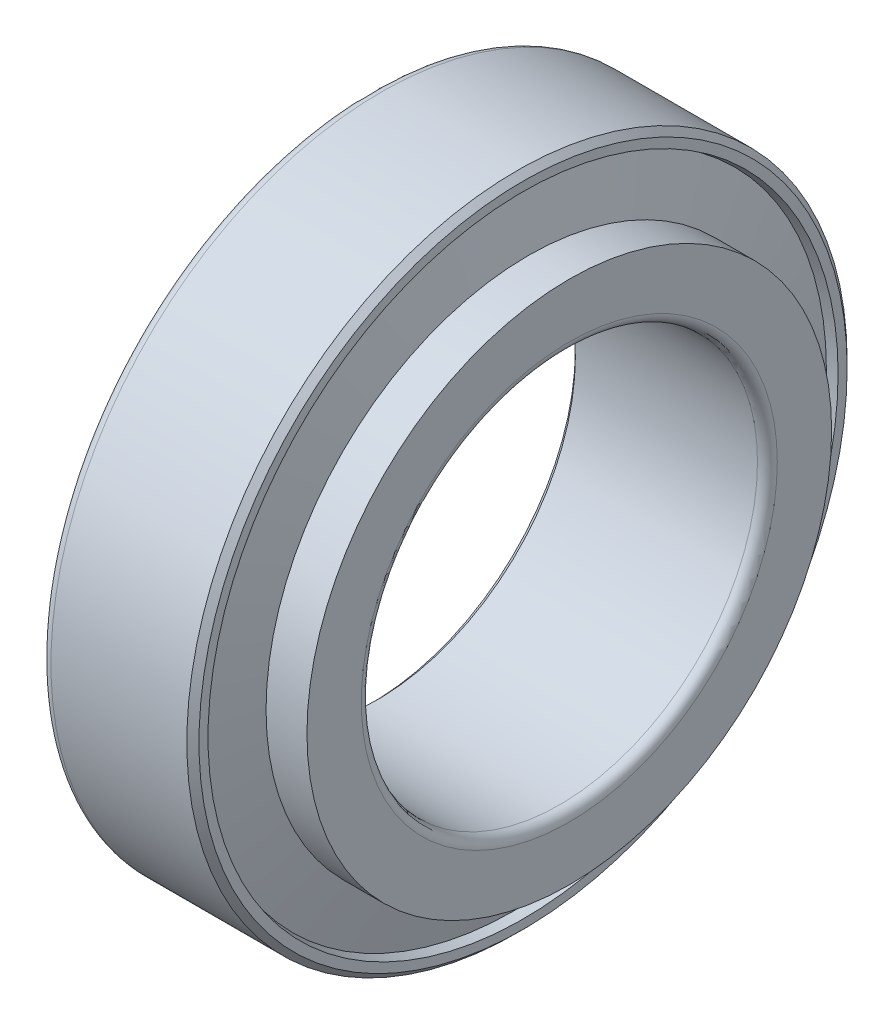
SolidWorks part; units mm, degrees
revolve "OuterRace" add sketch "OutRacSke" angle 360 about L5 other way angle 28.04 reverse direction yes
sketch "OutRacSke" plane through (0, 0, 0) normal (0, 0, 1) x (1, 0, 0)
  line L0 (-7, 47.7097) -> (-30, 41.7615)
  line L1 (-30, 41.7615) -> (-30, 48.5)
  line L2 (-28.5, 50) -> (-7.92, 50)
  line L3 (-7.92, 50) -> (-7, 49.08)
  line L4 (-7, 49.08) -> (-7, 47.7097)
  line L5 (-42.5, 0) -> (42.5, 0) construction
  arc A0 (-30, 48.5) -> (-28.5, 50) centre (-28.5, 48.5) cw
  dimension "D8" = 45
  dimension "Tangle" = 14.5
ref_plane "Plane1" through (0, 0, 0) normal (0, 0, 1) x (1, 0, 0)
ref_plane "Plane2" through (0, 0, 0) normal (0, 1, 0) x (1, 0, 0)
ref_plane "Plane3" through (0, 0, 0) normal (1, 0, 0) x (0, 0, -1)
sketch "Clipboard" plane through (0, 0, 0) normal (0, 0, 1) x (1, 0, 0)
  line L0 (0, 0) -> (10, 0) construction
  line L1 (0, 0) -> (83.4721, -2.9149)
  line L2 (0, 0) -> (59.9634, 2.094)
  line L3 (0, 0) -> (99.9391, -3.4899)
  line L4 (0, 0) -> (-20.6968, -0.3613)
  line L5 (0, 0) -> (-9, 30)
  dimension "Roller_diameter" = 9
  dimension "cyl_len" = 20.7
sketch "RolDetSke" plane through (0, 0, 0) normal (0, 0, 1) x (1, 0, 0)
  line L0 (-27.3733, 38.0035) -> (-28.5, 42.3602)
  line L1 (-27.3733, 38.0035) -> (-7.3326, 43.1864)
  line L2 (-8.4593, 47.543) -> (-7.3326, 43.1864)
  line L4 (-44.5664, 33.5571) -> (5.2024, 46.4281) construction
  line L5 (-8.4593, 47.543) -> (-28.5, 42.3602)
  line L9 (-7, 47.7097) -> (-30, 41.7615) construction
  dimension "Roller_diameter" = 9
  dimension "dy" = 42.3602
  dimension "D2" = 28.5
  dimension "cyl_len" = 20.7
revolve "RollerDetailed" [suppressed] add sketch "RolDetSke" angle 360 about L4 reverse direction yes
sketch "RolSimSke" plane through (0, 0, 0) normal (0, 0, 1) x (1, 0, 0)
  line L0 (0, 0) -> (-32, 0) construction
  line L1 (-28.5, 42.3602) -> (-8.4593, 47.543)
  line L2 (-28.5, 42.3602) -> (-26.2466, 33.6468)
  line L3 (-26.2466, 33.6468) -> (-6.2059, 38.8297)
  line L4 (-8.4593, 47.543) -> (-6.2059, 38.8297)
  dimension "Roller_diameter" = 9
  dimension "dy" = 42.3602
  dimension "dx" = 28.5
  dimension "Tangle" = 14.5
revolve "RollersSimplified" add sketch "RolSimSke" angle 360 about L0
ref_axis "Axis1" through (-50, 0, 0) along (1, 0, 0)
pattern_circular "RollersDetailed" [suppressed] count 2 every 180 about axis through (-50, 0, 0) along (1, 0, 0)
sketch "InsRacSke" plane through (0, 0, 0) normal (0, 0, 1) x (1, 0, 0)
  line L0 (-26.3517, 34.0968) -> (-30, 34.0968)
  line L1 (-30, 48.5) -> (-30, -48.5) construction
  line L2 (-30, 34.0968) -> (-30, 30.92)
  line L3 (-30, 30.92) -> (-29.08, 30)
  line L4 (-29.08, 30) -> (-1.5, 30)
  line L5 (0, 31.5) -> (0, 39.7297)
  line L6 (0, 39.7297) -> (-6.1947, 39.7297)
  line L7 (-6.1947, 39.7297) -> (-6.1947, 38.8297)
  line L8 (-6.1947, 38.8297) -> (-26.2353, 33.6468)
  line L9 (-26.2353, 33.6468) -> (-26.3517, 34.0968)
  line L10 (-42.5, 0) -> (42.5, 0) construction
  arc A0 (-1.5, 30) -> (0, 31.5) centre (-1.5, 31.5) ccw
  dimension "Tangle" = 14.5
  dimension "cyl_len" = 20.7
  dimension "dy" = 33.6468
  dimension "dx" = 26.2353
  dimension "D11" = 45
  dimension "D2" = 30
revolve "InnerRace" add sketch "InsRacSke" angle 360 about L10 reverse direction yes
sketch "CagSpiSke" plane through (0, 0, 0) normal (0, 0, 1) x (1, 0, 0)
  line L3 (-6.3306, 43.2348) -> (-27.3733, 37.7928)
  line L4 (-27.804, 37.0616) -> (-27.5035, 35.8999)
  line L6 (-42.5, 0) -> (42.5, 0) construction
  arc A1 (-27.3733, 37.7928) -> (-27.804, 37.0616) centre (-27.2231, 37.2119) ccw
  dimension "Tangle" = 14.5
  dimension "radius" = 0.6
  dimension "dx" = 27.3733
  dimension "dy" = 37.7928
  dimension "offset" = 1.8
revolve "CageSpine" [suppressed] add sketch "CagSpiSke" angle 0.001 about L6 wall 1.5
equation "\"OD@OutRacSke\" = \"Race_OD@Clipboard\""
equation "\"cup_SID@OutRacSke\" = \"Race_ID@Clipboard\""
equation "\"chamfer@OutRacSke\" = \"cup_width@OutRacSke\" / 25"
equation "\"offset@OutRacSke\" = \"OA_width@Clipboard\""
equation "\"D2@RolDetSke\" = \"offset@OutRacSke\" - \"cup_radius@OutRacSke\""
equation "\"dy@RolDetSke\" =  ( ( \"Race_ID@Clipboard\" / 2 ) + ( \"cup_radius@OutRacSke\" ) * tan(\"Tangle@OutRacSke\" * 3.141592654/180) ) * 1.005"
equation "\"cyl_len@RolDetSke\" = \"cyl_len@Clipboard\""
equation "\"Roller_diameter@RolDetSke\" = \"Roller_diameter@Clipboard\""
equation "\"dx@RolSimSke\" = \"offset@OutRacSke\" - \"cup_radius@OutRacSke\""
equation "\"dy@RolSimSke\" =  ( ( \"Race_ID@Clipboard\" / 2 ) + ( \"cup_radius@OutRacSke\" ) * tan(\"Tangle@OutRacSke\" * 3.141592654/180) ) * 1.005"
equation "\"Cyl_Len@RolSimSke\" = \"cyl_len@Clipboard\""
equation "\"Roller_diameter@RolSimSke\" = \"Roller_diameter@Clipboard\""
equation "\"Bore@InsRacSke\" = \"Bore@Clipboard\""
equation "\"Tangle@InsRacSke\" = \"Tangle@OutRacSke\""
equation "\"cyl_len@InsRacSke\" = \"cyl_len@Clipboard\""
equation "\"chamfer@InsRacSke\" = \"chamfer@OutRacSke\""
equation "\"D2@InsRacSke\" = \"OA_width@Clipboard\""
equation "\"dx@InsRacSke\" = \"offset@OutRacSke\" - \"cup_radius@OutRacSke\" -  (  \"Roller_diameter@Clipboard\" * 1.005 )  * sin(\"Tangle@InsRacSke\" * 3.141592654/180)"
equation "\"dy@InsRacSke\" = ( ( \"Race_ID@Clipboard\" / 2 ) + ( \"cup_radius@OutRacSke\" ) * tan(\"Tangle@OutRacSke\" * 3.141592654/180) ) * 1.005 -  ( \"Roller_diameter@Clipboard\" )  * cos(\"Tangle@InsRacSke\" * 3.141592654/180) "
equation "\"front_groove@InsRacSke\" = \"Groove_dp@InsRacSke\" / 2"
equation "\"Tangle@CagSpiSke\" = \"Tangle@OutRacSke\""
equation "\"dx@CagSpiSke\" = ( \"offset@OutRacSke\" - \"cup_radius@OutRacSke\" ) -  (  \"Roller_diameter@Clipboard\" / 2  )  * sin(\"Tangle@InsRacSke\" * 3.141592654/180)"
equation "\"dy@CagSpiSke\" = ( ( \"Race_ID@Clipboard\" / 2 ) + ( \"cup_radius@OutRacSke\" ) * tan(\"Tangle@OutRacSke\" * 3.141592654/180) )  -  ( \"Roller_diameter@Clipboard\" / 2 )  * cos(\"Tangle@InsRacSke\" * 3.141592654/180) "
equation "\"length@CagSpiSke\" = \"cyl_len@Clipboard\" * 1.05"
equation "\"offset@CagSpiSke\" = \"Roller_diameter@Clipboard\" / 5"
equation "\"radius@CagSpiSke\" = \"offset@CagSpiSke\" / 3"
equation "\"D3@CageSpine\" = \"Roller_diameter@Clipboard\" / 6"
equation "\"Max_count@Clipboard\" = int( 3.14159265 / atn(( \"Roller_diameter@Clipboard\" / 2) / sqr( \"dy@CagSpiSke\"  *  \"dy@CagSpiSke\" - ( \"Roller_diameter@Clipboard\" / 2) *  ( \"Roller_diameter@Clipboard\" / 2))))"
equation "\"Max_count@Clipboard\" = ((sgn( \"Max_count@Clipboard\" - \"Count@Clipboard\" )-1)*( \"Max_count@Clipboard\" - \"Count@Clipboard\" ))/-2+ \"Count@Clipboard\""
equation "\"Count@RollersDetailed\" = int( \"Show_count@Clipboard\" ) "
equation "\"Count@RollersDetailed\" = ((sgn( \"Count@RollersDetailed\" - \"Max_count@Clipboard\" )-1)*( \"Count@RollersDetailed\" - \"Max_count@Clipboard\" ))/-2+ \"Max_count@Clipboard\""
equation "\"Count@RollersDetailed\" = ((sgn( \"Count@RollersDetailed\" - \"Min_count@Clipboard\" )+1)*( \"Count@RollersDetailed\" - \"Min_count@Clipboard\"))/2 +\"Min_count@Clipboard\""
equation "\"Angle@RollersDetailed\" = 360.0 / \"Max_count@Clipboard\""
equation "\"Angle@CageSpine\" =  \"Angle@RollersDetailed\" * ( \"Count@RollersDetailed\" -1 + int( \"Count@RollersDetailed\" / \"Max_count@Clipboard\" ) )  + 0.001 -  int( \"Count@RollersDetailed\" / \"Max_count@Clipboard\" ) * 0.001"
equation "\"Angle@CageSpine\" =  \"Angle@CageSpine\" * int( \"Min_count@Clipboard\" / 2) + int(1 / \"Min_count@Clipboard\")  * 0.001"
equation "\"Tangle@RolSimSke\" = \"Tangle@OutRacSke\""
